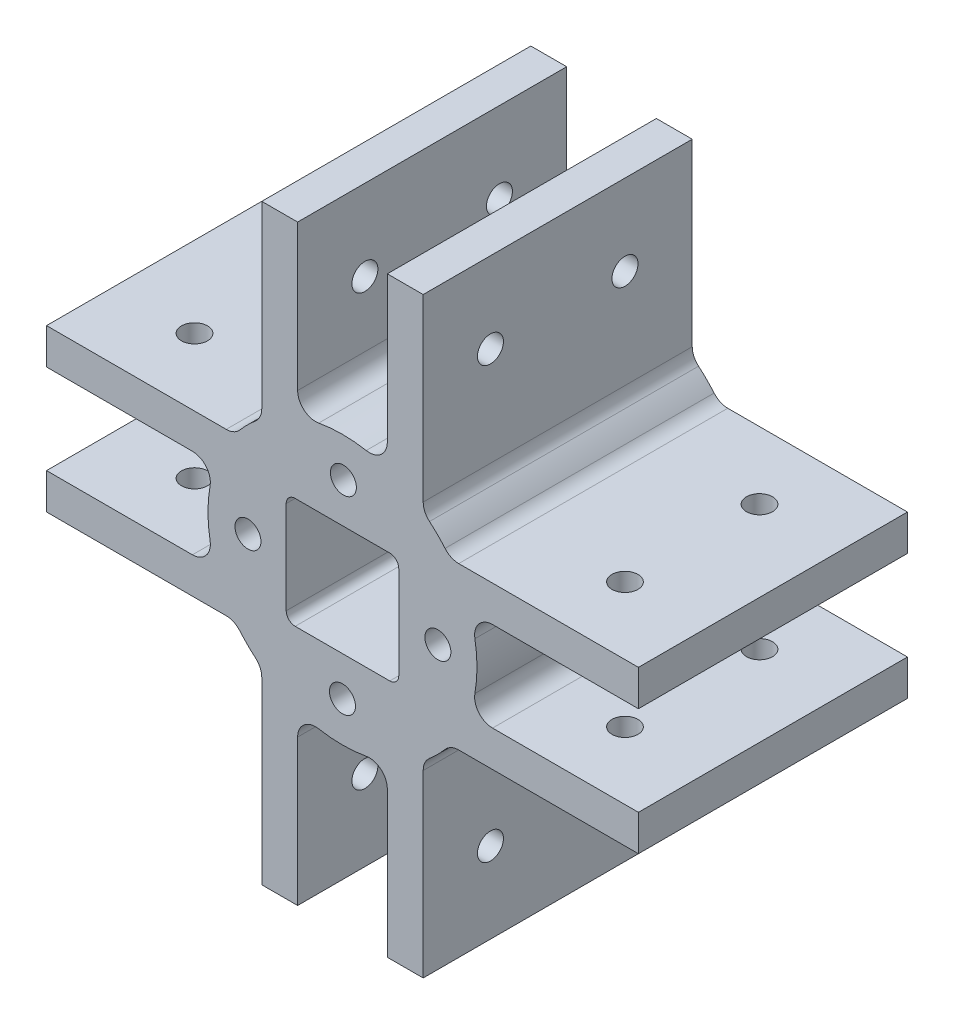
SolidWorks part; units mm, degrees
ref_plane "Front Plane" through (0, 0, 0) normal (0, 0, 1) x (1, 0, 0)
ref_plane "Top Plane" through (0, 0, 0) normal (0, 1, 0) x (1, 0, 0)
ref_plane "Right Plane" through (0, 0, 0) normal (1, 0, 0) x (0, 0, -1)
sketch "Sketch1" plane through (0, 0, 0) normal (0, 0, 1) x (1, 0, 0)
  circle A0 centre (0, 0) radius 15
  dimension "D2" = 30
extrude "Boss-Extrude1" add sketch "Sketch1" along normal mid plane 30
sketch "Sketch4" plane through (0, 0, 15) normal (0, 0, 1) x (1, 0, 0)
  line L0 (16.5, 0) -> (-16.5, 0) construction
  line L2 (-9, 0) -> (-5, 0)
  line L3 (0, 0) -> (0, 15.8331) construction
  line L4 (-9, 0) -> (-9, 33)
  line L5 (-9, 33) -> (-5, 33)
  line L6 (-5, 0) -> (-5, 33)
  line L7 (0, -16.5) -> (0, 16.5) construction
  line L8 (9, 33) -> (5, 33)
  line L9 (5, 0) -> (5, 33)
  line L10 (9, 0) -> (5, 0)
  line L11 (9, 0) -> (9, 33)
  dimension "D1" = 33
  dimension "D3" = 5
extrude "Boss-Extrude3" add sketch "Sketch4" against normal up to surface (30 mm away) up to face at (15, 0, -15)
fillet "Fillet2" radius 2 4 edges at (9, 12, 0) (5, 14.1421, 0) (-5, 14.1421, 0) (-9, 12, 0)
pattern_circular "CirPattern7" count 4 over 360 about axis through (0, 0, 15) along (0, 0, 1) of "Boss-Extrude3", "Fillet2"
sketch "Sketch7" plane through (-9, 0, 0) normal (-1, 0, 0) x (0, 0, 1)
  line L0 (-15, 33) -> (15, 33) construction
  line L1 (-15, 12.9615) -> (-15, 33) construction
  circle A0 centre (-7.5, 24) radius 1.45
  circle A1 centre (7.5, 24) radius 1.45
  circle A2 centre (22.5, 24) radius 1.45
  circle A3 centre (37.5, 24) radius 1.45
  circle A4 centre (52.5, 24) radius 1.45
  dimension "D1" = 2.9
  dimension "D2" = 9
  dimension "D3" = 7.5
  dimension "D4" = 5
extrude "Cut-Extrude2" cut sketch "Sketch7" against normal blind 27
pattern_circular "CirPattern9" count 4 over 360 about axis through (0, 0, 15) along (0, 0, 1) of "Cut-Extrude2"
sketch "Sketch8" plane through (0, 0, 15) normal (0, 0, 1) x (1, 0, 0)
  line L2 (-6.275, 6.175) -> (6.275, 6.175)
  line L3 (-6.275, 6.175) -> (-6.275, -6.175)
  line L4 (-6.275, -6.175) -> (6.275, -6.175)
  line L5 (6.275, 6.175) -> (6.275, -6.175)
  line L6 (-6.275, 6.175) -> (6.275, -6.175) construction
  line L7 (-6.275, -6.175) -> (6.275, 6.175) construction
  point P5 (0, 0)
  point P14 (0, 0)
  dimension "D1" = 12.55
  dimension "D2" = 12.35
extrude "Cut-Extrude3" cut sketch "Sketch8" against normal up to next
sketch "Sketch9" plane through (0, 0, 15) normal (0, 0, 1) x (1, 0, 0)
  line L0 (16.5, 0) -> (-16.5, 0) construction
  line L1 (6.275, -6.175) -> (6.275, 6.175) construction
  circle A0 centre (10.6375, 0) radius 1.45
  circle A1 centre (0, -10.5375) radius 1.45
  circle A2 centre (-10.5375, 0.1) radius 1.45
  circle A3 centre (0.1, 10.6375) radius 1.45
  point P14 (0.05, 0.05)
  dimension "D1" = 2.9
  dimension "D2" = 4.3625
  dimension "D3" = 4
extrude "Cut-Extrude4" cut sketch "Sketch9" against normal blind 10
fillet "Fillet1" radius 1 4 edges at (-6.275, 6.175, 0) (6.275, 6.175, 0) (6.275, -6.175, 0) (-6.275, -6.175, 0)
mirror "Mirror1" about plane through (0, 0, 0) normal (0, 0, 1) of "Cut-Extrude4"
equation "\"drumDiameter\"= 30"
equation "\"D2@Sketch1\"=\"drumDiameter\""
equation "\"drumLength\"= 30"
equation "\"D1@Sketch4\"=\"drumDiameter\"*(0.5+\"drumAbove\")"
equation "\"foamThickness\"= 10"
equation "\"D3@Sketch4\"=\"foamThickness\"/2"
equation "\"drumAbove\"= 0.6"
equation "\"D2@Sketch7\"=\"drumDiameter\"*\"drumAbove\"/2"
equation "\"holderThicc\"= 4"
equation "\"D2@Sketch4\"=\"holderThicc\""
equation "\"D1@Boss-Extrude1\"=\"drumLength\""
equation "\"squareBarLength\"= 12.55"
equation "\"D1@Sketch8\"=\"squareBarLength\""
equation "\"D2@Sketch9\"=(\"drumDiameter\"/2-\"squareBarLength\"/2)/2"
equation "\"squareBarShortLen\"= 12.35"
equation "\"D2@Sketch8\"=\"squareBarShortLen\""
